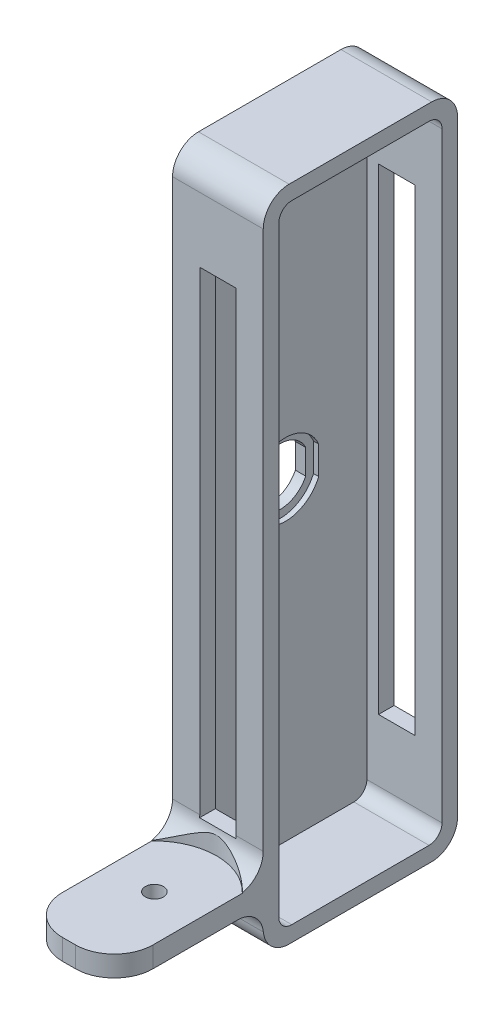
SolidWorks part; units mm, degrees
material "Titanium Ti-8Mn, Annealed"
ref_plane "Front Plane" through (0, 0, 0) normal (0, 0, 1) x (1, 0, 0)
ref_plane "Top Plane" through (0, 0, 0) normal (0, 1, 0) x (1, 0, 0)
ref_plane "Right Plane" through (0, 0, 0) normal (1, 0, 0) x (0, 0, -1)
sketch "Sketch3" plane through (0, 0, 0) normal (1, 0, 0) x (0, 0, -1)
  line L1 (-37.5, -127) -> (37.5, -127)
  line L2 (-37.5, -127) -> (-37.5, 127)
  line L3 (-37.5, 127) -> (37.5, 127)
  line L4 (37.5, -127) -> (37.5, 127)
  line L5 (-37.5, -127) -> (37.5, 127) construction
  line L6 (-37.5, 127) -> (37.5, -127) construction
  point P0 (0, 0)
  dimension "D1" = 254
  dimension "D2" = 75
extrude "Boss-Extrude2" add sketch "Sketch3" along normal blind 35
shell "Shell2" thickness 6 removed face at (35, 0, 0)
sketch "Sketch4" plane through (6, 0, 0) normal (1, 0, 0) x (0, 0, -1)
  line L1 (12.9, -5.4397) -> (12.9, 5.4397)
  line L3 (-12.6, -6.1025) -> (-12.6, 6.1025)
  arc A0 (-12.6, -6.1025) -> (12.9, -5.4397) centre (0, 0) ccw
  arc A1 (12.9, 5.4397) -> (-12.6, 6.1025) centre (0, 0) ccw
  point P9 (-12.6, 0)
  dimension "D1" = 12.9
  dimension "D2" = 14
extrude "Cut-Extrude1" cut sketch "Sketch4" against normal blind 2
sketch "Sketch5" plane through (4, 0, 0) normal (1, 0, 0) x (0, 0, -1)
  line L1 (9.9, -4.7948) -> (9.9, 4.7948)
  line L3 (-9.9, -4.7948) -> (-9.9, 4.7948)
  arc A1 (9.9, 4.7948) -> (-9.9, 4.7948) centre (0, 0) ccw
  arc A2 (-9.9, -4.7948) -> (9.9, -4.7948) centre (0, 0) ccw
  point P11 (-9.9, 0)
extrude "Cut-Extrude2" cut sketch "Sketch5" against normal through all
sketch "Sketch6" plane through (0, 0, 37.5) normal (0, 0, 1) x (1, 0, 0)
  line L0 (17.5, -127) -> (17.5, -92) construction
  line L1 (35, -127) -> (0, -127) construction
  line L2 (17.5, -92) -> (10.5, -92) construction
  line L3 (10.5, -92) -> (10.5, 92)
  line L4 (10.5, 92) -> (24.5, 92)
  line L5 (24.5, 92) -> (24.5, -92)
  line L6 (24.5, -92) -> (10.5, -92)
  line L7 (35, 127) -> (0, 127) construction
  dimension "D1" = 35
  dimension "D2" = 35
extrude "Cut-Extrude3" cut sketch "Sketch6" against normal through all
fillet "Fillet1" radius 10 4 edges at (17.5, -127, 37.5) (17.5, -127, -37.5) (17.5, 127, -37.5) (17.5, 127, 37.5)
fillet "Fillet2" radius 5 4 edges at (20.5, -121, -31.5) (20.5, -121, 31.5) (20.5, 121, -31.5) (20.5, 121, 31.5)
ref_plane "Plane1" through (0, 0, 7.5) normal (0, 0, 1) x (1, 0, 0)
sketch "Sketch12" plane through (35, 0, 0) normal (1, 0, 0) x (0, 0, -1)
  line L2 (-95, -109) -> (-37.5, -109)
  line L3 (-37.5, 117) -> (-37.5, -117) construction
  line L6 (-37.5, -109) -> (-37.5, -101)
  line L7 (-37.5, -101) -> (-95, -101)
  line L8 (-95, -101) -> (-95, -109)
extrude "Boss-Extrude4" add sketch "Sketch12" against normal up to surface (35 mm away) up to face at (0, 0, 0)
fillet "Fillet5" radius 10 2 edges at (17.5, -109, 37.5) (17.5, -101, 37.5)
fillet "Fillet6" radius 15 2 edges at (0, -105, 95) (35, -105, 95)
sketch "Sketch14" plane through (0, -101, 0) normal (0, 1, 0) x (1, 0, 0)
  line L0 (0, 0) -> (0, -37.5) construction
  line L1 (0, -37.5) -> (0, -62) construction
  line L2 (0, -47.5) -> (0, -80) construction
  line L3 (0, -62) -> (17.5, -62) construction
  circle A0 centre (17.5, -62) radius 4
hole_wizard "M8x1.0 Tapped Hole1" positions "3DSketch1" profile "Sketch15" tap size "M8x1.0" standard "ANSI Metric"
sketch3d "3DSketch1"
  point P0 (17.5, -101, 62)
sketch "Sketch15" plane through (17.5, -101, 62) normal (1, 0, 0) x (0, 0, 1)
  line L0 (0, 0) -> (0, 10.103)
  line L1 (0, 10.103) -> (3.5, 8)
  line L2 (3.5, 8) -> (3.5, 0)
  line L5 (3.5, 0) -> (0, 0)
  line L10 (0, 10.103) -> (-3.5, 8) construction
  line L11 (0, -6.35) -> (0, 107.95) construction
  dimension "Tap Drill Dia." = 7
  dimension "Tap Drill Depth" = 8
  dimension "Drill Angle" = 118
cosmetic thread "Hole Thread1" parameters "D1"=8, "D2"=8
sketch "Sketch16" plane through (0, -101, 0) normal (0, 1, 0) x (1, 0, 0)
  circle A0 centre (17.5, -62) radius 24
extrude "Cut-Extrude4" cut sketch "Sketch16" along normal blind 91
